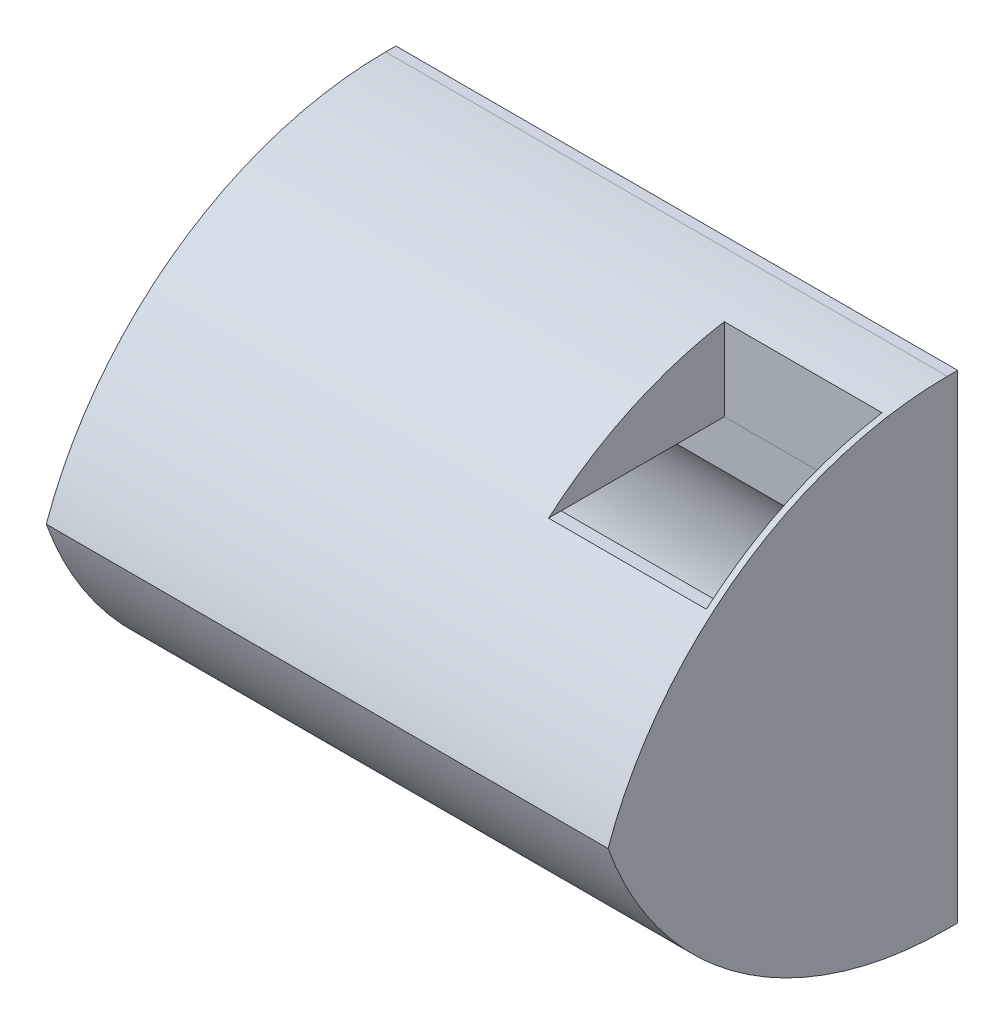
SolidWorks part; units mm, degrees
ref_plane "Alzado" through (0, 0, 0) normal (0, 0, 1) x (1, 0, 0)
ref_plane "Planta" through (0, 0, 0) normal (0, 1, 0) x (1, 0, 0)
ref_plane "Vista lateral" through (0, 0, 0) normal (1, 0, 0) x (0, 0, -1)
sketch "Croquis1" plane through (0, 0, 0) normal (0, 0, 1) x (1, 0, 0)
  line L0 (-69.2575, 15.7315) -> (56.7425, 15.7315) construction
  line L5 (-36.3466, 15.7315) -> (-74.9254, 15.7315)
  line L6 (-36.3466, 15.7315) -> (-36.3466, -30.7607)
  line L7 (-36.3466, -30.7607) -> (-74.9254, -30.7607)
  line L10 (-74.9254, 15.7315) -> (-36.3466, 15.7315)
  line L11 (-74.9254, 15.7315) -> (-74.9254, -30.7607)
  line L12 (-74.9254, -30.7607) -> (-36.3466, -30.7607)
  line L13 (-36.3466, 15.7315) -> (-36.3466, -30.7607)
extrude "Saliente-Extruir1" add sketch "Croquis1" along normal blind 36 contours L5 L11 L7 L6 region at (-55.636, -7.5146, 0)
sketch "Croquis2" plane through (-74.9254, 0, 0) normal (-1, 0, 0) x (0, 0, 1)
  circle A1 centre (15.0351, -8.3176) radius 13.723
extrude "Cortar-Extruir1" cut sketch "Croquis2" against normal blind 54
fillet "Redondeo1" radius 35 2 edges at (-55.636, 15.7315, 36) (-55.636, -30.7607, 36)
sketch "Croquis3" plane through (-36.3466, 0, 0) normal (1, 0, 0) x (0, 0, -1)
  line L3 (0, 15.7315) -> (-1, 15.7315)
  line L4 (-1, -30.7607) -> (0, -30.7607)
  line L5 (0, -30.7607) -> (0, 15.7315)
  line L6 (0, 15.7315) -> (-1, 15.7315)
  line L7 (-1, -30.7607) -> (0, -30.7607)
  line L8 (0, -30.7607) -> (0, 15.7315)
  arc A2 (-1, 15.7315) -> (-33.9674, -7.5146) centre (-1, -19.2685) ccw
  arc A3 (-33.9674, -7.5146) -> (-1, -30.7607) centre (-1, 4.2393) ccw
  arc A4 (-1, 15.7315) -> (-33.9674, -7.5146) centre (-1, -19.2685) ccw
  arc A5 (-33.9674, -7.5146) -> (-1, -30.7607) centre (-1, 4.2393) ccw
  dimension "D1" = 0
extrude "Saliente-Extruir2" add sketch "Croquis3" along normal blind 16
sketch "Croquis4" plane through (-36.3466, 0, 0) normal (-1, 0, 0) x (0, 0, 1)
  circle A1 centre (15.0351, -8.3176) radius 13.723
  circle A2 centre (15.0351, -8.3176) radius 13.723
  dimension "D1" = 0
extrude "Cortar-Extruir2" cut sketch "Croquis4" against normal blind 14
sketch "Croquis5" plane through (-74.9254, 0, 0) normal (-1, 0, 0) x (0, 0, 1)
  line L1 (6.6738, 2.5641) -> (22.6106, 2.5641)
  line L2 (6.6738, 2.5641) -> (6.6738, 7.257)
  line L3 (6.6738, 7.257) -> (22.6106, 7.257)
  line L4 (22.6106, 2.5641) -> (22.6106, 7.257)
  circle A0 centre (15.0351, -8.3176) radius 13.723 construction
  dimension "D1" = 15.9368
  dimension "D2" = 4.693
extrude "Cortar-Extruir3" cut sketch "Croquis5" against normal blind 54
sketch "Croquis6" plane through (0, 7.257, 0) normal (0, -1, 0) x (1, 0, 0)
  line L1 (-20.9374, 6.7634) -> (-36.2604, 6.7634)
  line L2 (-20.9374, 6.7634) -> (-20.9374, 25.7709)
  line L3 (-20.9374, 25.7709) -> (-36.2604, 25.7709)
  line L4 (-36.2604, 6.7634) -> (-36.2604, 25.7709)
extrude "Cortar-Extruir4" cut sketch "Croquis6" against normal blind 54
sketch "Croquis7" plane through (-74.9254, 0, 0) normal (-1, 0, 0) x (0, 0, 1)
  line L3 (1, 15.7315) -> (0, 15.7315)
  line L4 (0, 15.7315) -> (0, -30.7607)
  line L5 (0, -30.7607) -> (1, -30.7607)
  line L6 (1, 15.7315) -> (0, 15.7315)
  line L7 (0, 15.7315) -> (0, -30.7607)
  line L8 (0, -30.7607) -> (1, -30.7607)
  circle A0 centre (15.4988, -8.5455) radius 13.9461
  arc A2 (1, -30.7607) -> (33.9674, -7.5146) centre (1, 4.2393) ccw
  arc A3 (33.9674, -7.5146) -> (1, 15.7315) centre (1, -19.2685) ccw
  arc A4 (1, -30.7607) -> (33.9674, -7.5146) centre (1, 4.2393) ccw
  arc A5 (33.9674, -7.5146) -> (1, 15.7315) centre (1, -19.2685) ccw
  dimension "D2" = 27.8921
  dimension "D1" = 0
